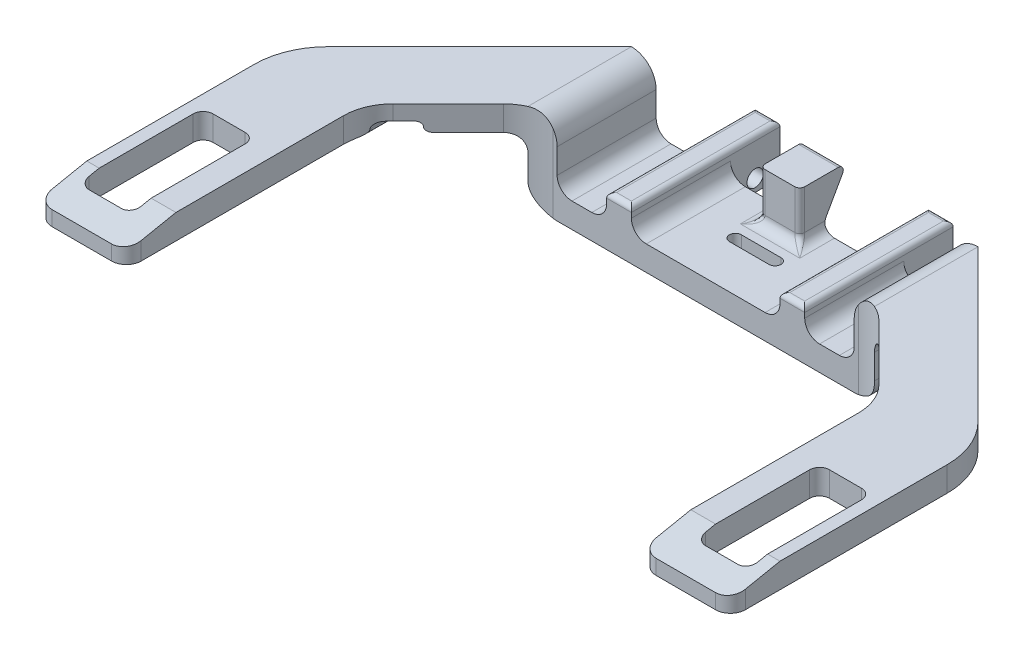
SolidWorks part; units mm, degrees
material "PMMA"
ref_plane "前视基准面" through (0, 0, 0) normal (0, 0, 1) x (1, 0, 0)
ref_plane "上视基准面" through (0, 0, 0) normal (0, 1, 0) x (1, 0, 0)
ref_plane "右视基准面" through (0, 0, 0) normal (1, 0, 0) x (0, 0, -1)
sketch "Sketch1" plane through (0, 0, 0) normal (0, 1, 0) x (1, 0, 0)
  line L0 (0, 0) -> (0, -30)
  line L1 (0, -30) -> (70, -30)
  line L2 (70, -30) -> (70, 0)
  line L3 (70, 0) -> (0, 0)
  line L4 (-8.4439, -20) -> (85.4448, -20) construction
  line L5 (35, 10.0792) -> (35, -39.1296) construction
  line L6 (31, 10.0792) -> (31, -39.1296) construction
  line L7 (39, 10.0792) -> (39, -39.1296) construction
  line L8 (31, -20) -> (39, -20) construction
  line L9 (31, -18.8) -> (39, -18.8)
  line L10 (31, -21.2) -> (39, -21.2)
  arc A0 (31, -18.8) -> (31, -21.2) centre (31, -20) ccw
  arc A1 (39, -21.2) -> (39, -18.8) centre (39, -20) ccw
  point P15 (35, -20)
  dimension "D7" = 1.2
  dimension "D1" = 70
  dimension "D2" = 30
  dimension "D3" = 20
  dimension "D4" = 35
  dimension "D8" = 8
  dimension "D5" = 4
  dimension "D6" = 4
extrude "Boss-Extrude1" add sketch "Sketch1" along normal blind 5
sketch "Sketch2" plane through (0, 5, 0) normal (0, 1, 0) x (1, 0, 0)
  line L0 (35, 1.902) -> (35, -15.3658) construction
  line L2 (50, 0) -> (50, -10)
  line L4 (50, 0) -> (20, 0)
  line L5 (70, 0) -> (0, 0) construction
  line L6 (20, 0) -> (20, -10)
  line L7 (20, -10) -> (50, -10)
  line L8 (0, 0) -> (0, -30) construction
  point P4 (22.5, 2.2922)
  point P5 (22.5, -33.5605)
  dimension "D1" = 35
  dimension "D3" = 30
  dimension "D4" = 10
  dimension "D2" = 15
extrude "Cut-Extrude1" cut sketch "Sketch2" against normal through all
sketch "Sketch3" plane through (0, 5, 0) normal (0, 1, 0) x (1, 0, 0)
  line L0 (35, 1.6581) -> (35, -30.8288) construction
  line L1 (70, -30) -> (70, 0) construction
  line L2 (15, 0) -> (15, -10)
  line L3 (20, 0) -> (0, 0) construction
  line L4 (15, -10) -> (0, -10)
  line L5 (0, 0) -> (0, -30) construction
  line L6 (0, -10) -> (0, 0)
  line L7 (0, 0) -> (15, 0)
  line L8 (20, 0) -> (20, -10) construction
  line L9 (70, -10) -> (70, 0)
  line L10 (55, -10) -> (70, -10)
  line L11 (55, 0) -> (55, -10)
  line L12 (70, 0) -> (55, 0)
  dimension "D1" = 35
  dimension "D2" = 5
  dimension "D3" = 10
extrude "Cut-Extrude2" cut sketch "Sketch3" against normal through all
sketch "Sketch4" plane through (15, 0, 0) normal (-1, 0, 0) x (0, 0, 1)
  line L0 (-0.9926, 2.5) -> (11.5088, 2.5) construction
  line L1 (5, 6.857) -> (5, -1.7142) construction
  line L2 (10, 0) -> (10, 5) construction
  line L3 (10, 0) -> (0, 0) construction
  circle A0 centre (5, 2.5) radius 1.65
  dimension "D3" = 3.3
  dimension "D1" = 5
  dimension "D2" = 2.5
extrude "Cut-Extrude3" cut sketch "Sketch4" against normal through all
sketch "Sketch5" plane through (0, 5, 0) normal (0, 1, 0) x (1, 0, 0)
  line L0 (0, -10) -> (0, -30)
  line L1 (0, -30) -> (5, -30)
  line L2 (0, -30) -> (70, -30) construction
  line L3 (5, -30) -> (5, -10)
  line L4 (0, -10) -> (15, -10) construction
  line L5 (5, -10) -> (0, -10)
  line L6 (35, -8.0002) -> (35, -35.219) construction
  line L7 (70, -30) -> (70, -10) construction
  line L8 (65, -30) -> (65, -10)
  line L9 (70, -30) -> (65, -30)
  line L10 (70, -10) -> (70, -30)
  line L11 (65, -10) -> (70, -10)
  dimension "D2" = 5
  dimension "D1" = 35
extrude "Boss-Extrude2" add sketch "Sketch5" along normal blind 13
sketch "Sketch6" plane through (0, 18, 0) normal (0, 1, 0) x (1, 0, 0)
  line L0 (35, -2.5369) -> (35, -39.4628) construction
  line L1 (70, -30) -> (70, -10) construction
  line L2 (0, -10) -> (0, -30)
  line L5 (-17, -51.1421) -> (-17, -92)
  line L6 (-20, -95) -> (-32, -95)
  line L7 (-35, -92) -> (-35, -51.2132)
  line L9 (-30.6066, -40.6066) -> (0, -10)
  line L18 (0, -30) -> (-14.0711, -44.0711)
  line L19 (0, -30) -> (5, -30) construction
  line L27 (90, -95) -> (102, -95)
  line L28 (87, -51.1421) -> (87, -92)
  line L29 (70, -30) -> (84.0711, -44.0711)
  line L30 (70, -10) -> (70, -30)
  line L31 (100.6066, -40.6066) -> (70, -10)
  line L32 (105, -92) -> (105, -51.2132)
  arc A2 (-32, -95) -> (-35, -92) centre (-32, -92) cw
  arc A3 (-17, -92) -> (-20, -95) centre (-20, -92) cw
  arc A12 (-17, -51.1421) -> (-14.0711, -44.0711) centre (-7, -51.1421) cw
  arc A18 (-35, -51.2132) -> (-30.6066, -40.6066) centre (-20, -51.2132) cw
  arc A19 (102, -95) -> (105, -92) centre (102, -92) ccw
  arc A20 (87, -92) -> (90, -95) centre (90, -92) ccw
  arc A21 (87, -51.1421) -> (84.0711, -44.0711) centre (77, -51.1421) ccw
  arc A22 (105, -51.2132) -> (100.6066, -40.6066) centre (90, -51.2132) ccw
  point P21 (-35, -95)
  point P24 (-17, -95)
  dimension "D9" = 3
  dimension "D10" = 10
  dimension "D4" = 15
  dimension "D1" = 35
  dimension "D2" = 85
  dimension "D3" = 18
  dimension "D5" = 17
  dimension "D6" = 45
  dimension "D7" = 135
extrude "Boss-Extrude3" add sketch "Sketch6" against normal blind 5
chamfer "Chamfer1" distance 2 distance2 10 1 edges at (-26, 18, 95) tangent propagation no first distance on face at (-26, 15.5, 95)
sketch "Sketch10" plane through (0, 13, 0) normal (0, -1, 0) x (1, 0, 0)
  line L0 (-16, 49) -> (-16, 19)
  line L1 (-16, 19) -> (-11, 19)
  line L2 (-11, 19) -> (-11, 49)
  line L3 (-11, 49) -> (-16, 49)
  line L4 (35, 37.2075) -> (35, 1.2084) construction
  line L5 (50, 10) -> (50, 0) construction
  line L6 (0, 30) -> (70, 30) construction
  line L7 (81, 19) -> (81, 49)
  line L8 (86, 19) -> (81, 19)
  line L9 (86, 49) -> (86, 19)
  line L10 (81, 49) -> (86, 49)
  dimension "D1" = 15
  dimension "D2" = 5
  dimension "D3" = 30
  dimension "D4" = 46
  dimension "D5" = 19
extrude "Cut-Extrude6" cut sketch "Sketch10" against normal blind 2
sketch "Sketch11" plane through (0, 5, 0) normal (0, 1, 0) x (1, 0, 0)
  line L0 (35, -5.4766) -> (35, -41.6237) construction
  line L2 (39, -10) -> (31, -10)
  line L3 (20, -10) -> (50, -10) construction
  line L4 (31, -10) -> (31, -15)
  line L5 (31, -15) -> (39, -15)
  line L6 (39, -10) -> (39, -15)
  point P11 (35, -15)
  point P12 (35, -10)
  dimension "D2" = 4
  dimension "D3" = 5
extrude "Boss-Extrude5" add sketch "Sketch11" along normal blind 10
fillet "Fillet11" radius 2 3 edges at (39, 5, 12.5) (31, 5, 12.5) (35, 5, 15)
sketch "Sketch12" plane through (0, 13, 0) normal (0, -1, 0) x (1, 0, 0)
  line L0 (92, 87) -> (92, 66)
  line L1 (94, 64) -> (100.5, 64)
  line L2 (102.5, 66) -> (102.5, 87)
  line L3 (100.5, 89) -> (94, 89)
  line L4 (87, 51.1421) -> (87, 92) construction
  line L5 (105, 92) -> (105, 51.2132) construction
  line L6 (90, 95) -> (102, 95) construction
  line L7 (35, 3.6475) -> (35, 34.1833) construction
  line L8 (50, 10) -> (50, 0) construction
  line L9 (-32.5, 66) -> (-32.5, 87)
  line L10 (-24, 64) -> (-30.5, 64)
  line L11 (-22, 87) -> (-22, 66)
  line L12 (-30.5, 89) -> (-24, 89)
  arc A0 (92, 66) -> (94, 64) centre (94, 66) ccw
  arc A1 (100.5, 64) -> (102.5, 66) centre (100.5, 66) ccw
  arc A2 (102.5, 87) -> (100.5, 89) centre (100.5, 87) ccw
  arc A3 (92, 87) -> (94, 89) centre (94, 87) cw
  arc A4 (-30.5, 64) -> (-32.5, 66) centre (-30.5, 66) cw
  arc A5 (-22, 66) -> (-24, 64) centre (-24, 66) cw
  arc A6 (-32.5, 87) -> (-30.5, 89) centre (-30.5, 87) cw
  arc A7 (-22, 87) -> (-24, 89) centre (-24, 87) ccw
  point P14 (102.5, 64)
  point P17 (102.5, 89)
  dimension "D5" = 2
  dimension "D1" = 5
  dimension "D2" = 2.5
  dimension "D3" = 6
  dimension "D4" = 25
  dimension "D6" = 15
extrude "Cut-Extrude7" cut sketch "Sketch12" against normal through all
fillet "Fillet13" radius 1 8 edges at (-16, 13, 36.3916) (-16, 15, 36.3916) (-11, 13, 31) (-11, 15, 31) (86, 13, 36.3916) (86, 15, 36.3916) (81, 13, 31) (81, 15, 31)
fillet "Fillet14" radius 5 4 edges at (0, 0, 20) (70, 0, 20) (5, 18, 20) (65, 18, 20)
fillet "Fillet15" radius 3 4 edges at (0, 13, 20) (5, 5, 20) (65, 5, 20) (70, 13, 20)
chamfer "Chamfer2" distance 2 distance2 10 1 edges at (96, 18, 95) tangent propagation no first distance on face at (96, 15.5, 95)
fillet "Fillet16" radius 10 2 edges at (70, 14, 30) (0, 14, 30)
sketch "Sketch14" plane through (0, 5, 0) normal (0, 1, 0) x (1, 0, 0)
  line L0 (15, 0) -> (15, -30)
  line L1 (8, -30) -> (62, -30) construction
  line L2 (15, -30) -> (20, -30)
  line L3 (20, -30) -> (20, 0)
  line L4 (20, 0) -> (15, 0) construction
  line L5 (20, 0) -> (15, 0)
  line L6 (35, -30) -> (35, -35.5491) construction
  line L7 (50, -30) -> (50, 0)
  line L8 (55, -30) -> (50, -30)
  line L9 (55, 0) -> (55, -30)
  line L10 (50, 0) -> (55, 0)
  dimension "D1" = 0
extrude "Boss-Extrude6" add sketch "Sketch14" along normal blind 5
fillet "Fillet17" radius 1 8 edges at (17.5, 10, 30) (52.5, 10, 30) (15, 10, 15) (20, 10, 15) (55, 10, 15) (50, 10, 15) (17.5, 10, 0) (52.5, 10, 0)
sketch "Sketch16" plane through (31, 0, 0) normal (-1, 0, 0) x (0, 0, 1)
  line L0 (10, 15) -> (5.5, 15)
  line L1 (5.5, 15) -> (10, 7)
  line L2 (10, 7) -> (10, 15)
  dimension "D1" = 4.5
extrude "Boss-Extrude8" add sketch "Sketch16" against normal blind 8
fillet "Fillet18" radius 1 1 edges at (35, 15, 5.5)
fillet "Fillet19" radius 3 1 edges at (35, 7, 10)
fillet "Fillet20" radius 3 4 edges at (55, 5, 20) (50, 5, 20) (15, 5, 20) (20, 5, 20)
fillet "Fillet21" radius 1 4 edges at (39.5858, 5.5858, 15.5858) (30.4142, 5.5858, 15.5858) (39, 11, 15) (31, 11, 15)
